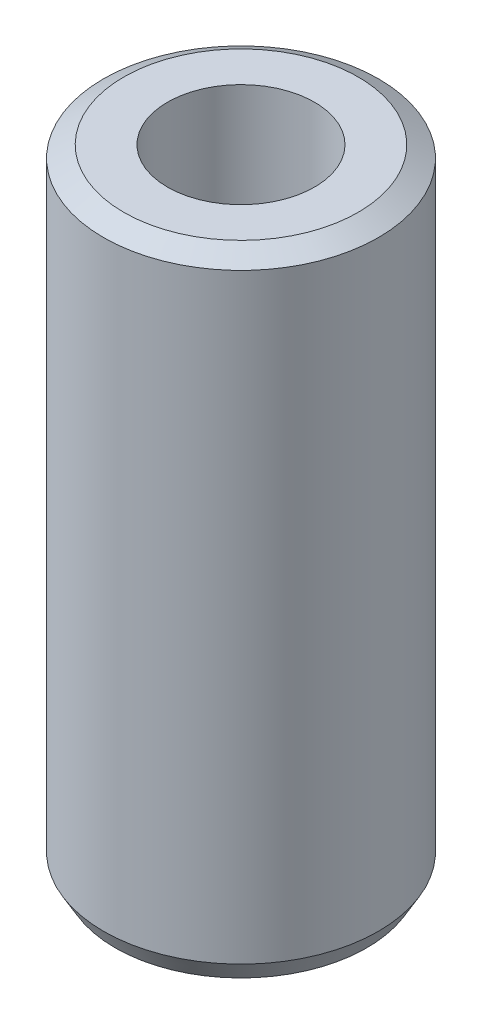
SolidWorks part; units mm, degrees
ref_plane "Front Plane" through (0, 0, 0) normal (0, 0, 1) x (1, 0, 0)
ref_plane "Top Plane" through (0, 0, 0) normal (0, 1, 0) x (1, 0, 0)
ref_plane "Right Plane" through (0, 0, 0) normal (1, 0, 0) x (0, 0, -1)
sketch "Sketch1" plane through (0, 0, 0) normal (0, 1, 0) x (1, 0, 0)
  circle A0 centre (0, 0) radius 27.5
  dimension "SHAFT_OD" = 55
extrude "Boss-Extrude1" add sketch "Sketch1" along normal blind 126.5472
sketch "Sketch2" plane through (0, 0, 0) normal (0, 1, 0) x (1, 0, 0)
  circle A0 centre (0, 0) radius 14.7147
  dimension "BORE_D" = 29.4293
extrude "Cut-Extrude1" cut sketch "Sketch2" along normal through all
chamfer "Chamfer1" distance 2.3387 angle 60 2 edges at (0, 126.5472, 27.5) (0, 0, 27.5) first distance on face at (0, 126.5472, 27.5) first distance on face at (0, 0, 14.7147)
